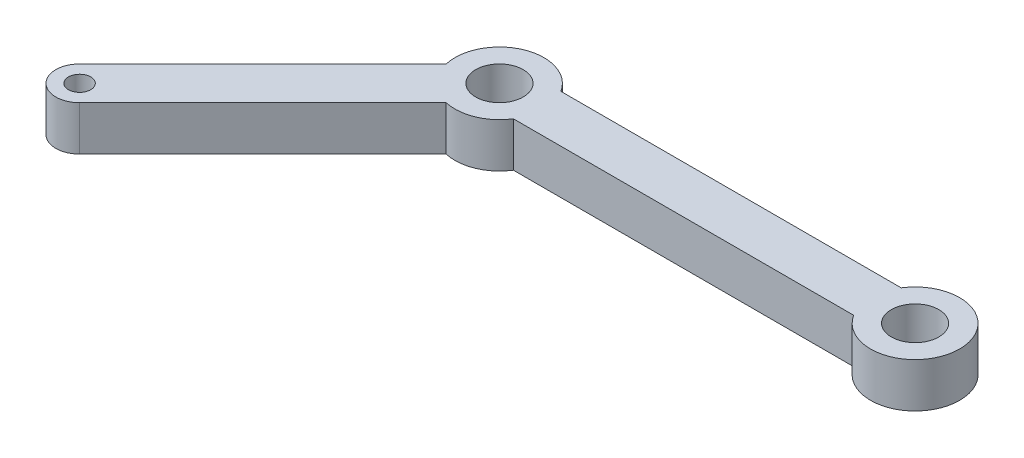
SolidWorks part; units mm, degrees
note: The reader was unsure of these and kept them because the rebuilt part matched: thickness of "基体-法兰1", "钣金6".
material "ABS"
ref_plane "前视基准面" through (0, 0, 0) normal (0, 0, 1) x (1, 0, 0)
ref_plane "上视基准面" through (0, 0, 0) normal (0, 1, 0) x (1, 0, 0)
ref_plane "右视基准面" through (0, 0, 0) normal (1, 0, 0) x (0, 0, -1)
sketch "草图1" plane through (0, 0, 0) normal (0, 1, 0) x (1, 0, 0)
  line L0 (-25.4623, 1.6) -> (-2.5377, 1.6)
  line L1 (-25.4623, -1.6) -> (-2.5377, -1.6)
  line L2 (-43.2735, -13.0108) -> (-30.9258, -0.6631)
  line L3 (-28.6631, -2.9258) -> (-41.0108, -15.2735)
  circle A0 centre (0, 0) radius 1.6
  arc A1 (-2.5377, -1.6) -> (-2.5377, 1.6) centre (0, 0) ccw
  circle A2 centre (-28, 0) radius 1.6
  arc A3 (-25.4623, 1.6) -> (-30.9258, -0.6631) centre (-28, 0) ccw
  circle A4 centre (-42.1421, -14.1421) radius 0.75
  arc A5 (-43.2735, -13.0108) -> (-41.0108, -15.2735) centre (-42.1421, -14.1421) ccw
  arc A6 (-28.6631, -2.9258) -> (-25.4623, -1.6) centre (-28, 0) ccw
  dimension "D1" = 3.2
  dimension "D2" = 6
  dimension "D3" = 3.2
  dimension "D4" = 6
  dimension "D5" = 28
  dimension "D6" = 1.5
  dimension "D7" = 3.2
  dimension "D8" = 20
  dimension "D9" = 135
base flange "基体-法兰1" sketch "草图1" thickness 3 reverse thickness direction no parameters "D1"=0.7366
sketch "折弯-线1" [suppressed] plane through (0, 0, 0) normal (0, 1, 0) x (1, 0, 0)
sketch "边界框1" [suppressed] plane through (0, 0, 0) normal (0, 1, 0) x (1, 0, 0)
sheet metal parameters "钣金6" thickness 3 parameters "D1"=0.7366
flat pattern "平板型式6" [suppressed]
sketch "折弯-线2" plane through (0, 0, 0) normal (0, 1, 0) x (1, 0, 0)
sketch3d "边界框2" [suppressed]
  line L0 (3.7118, -2.0545, 0) -> (-45.238, -16.1217, 0) construction
  line L1 (-0.234, 11.6754, 0) -> (-49.1837, -2.3918, 0) construction
  line L2 (3.7118, -2.0545, 0) -> (-0.234, 11.6754, 0) construction
  line L3 (-45.238, -16.1217, 0) -> (-49.1837, -2.3918, 0) construction
